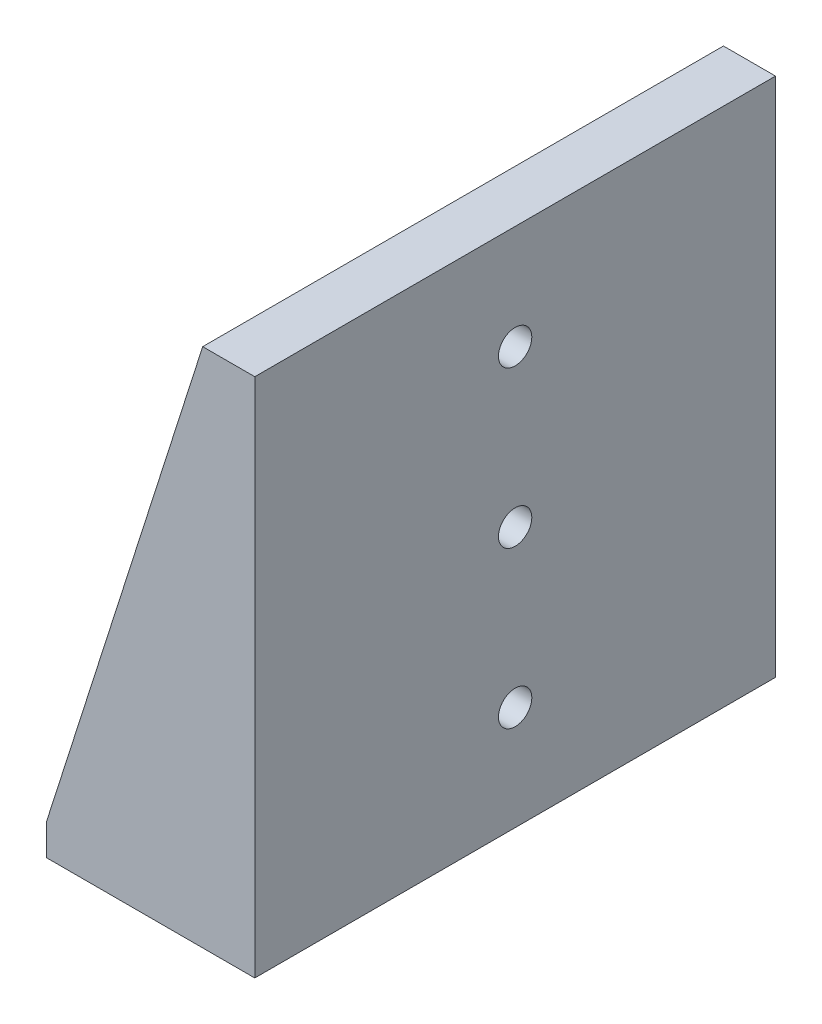
SolidWorks part; units mm, degrees
ref_plane "Front Plane" through (0, 0, 0) normal (0, 0, 1) x (1, 0, 0)
ref_plane "Top Plane" through (0, 0, 0) normal (0, 1, 0) x (1, 0, 0)
ref_plane "Right Plane" through (0, 0, 0) normal (1, 0, 0) x (0, 0, -1)
sketch "Sketch1" plane through (0, 0, 0) normal (0, 0, 1) x (1, 0, 0)
  line L0 (-10, 0) -> (10, 0)
  line L1 (-10, 0) -> (-10, 3)
  line L2 (-10, 3) -> (5, 50)
  line L3 (-10, 3) -> (23.3287, 3) construction
  line L4 (5, 50) -> (10, 50)
  line L5 (10, 0) -> (10, 50)
  point P4 (0, 0)
  dimension "D1" = 20
  dimension "D2" = 3
  dimension "D3" = 50
  dimension "D4" = 5
extrude "Boss-Extrude1" add sketch "Sketch1" along normal blind 50
sketch "Sketch3" plane through (-9.9445, 3.1738, 0) normal (-0.9527, 0.304, 0) x (0, 0, 1)
  line L0 (2.5, 49.1532) -> (2.5, -0.1824)
  line L1 (2.5, -0.1824) -> (47.5, -0.1824)
  line L2 (47.5, -0.1824) -> (47.5, 49.1532)
  line L3 (0, 49.1532) -> (0, -0.1824) construction
  line L4 (50, -0.1824) -> (0, -0.1824) construction
  line L5 (2.5, 49.1532) -> (47.5, 49.1532)
  line L6 (50, 49.1532) -> (0, 49.1532) construction
  line L7 (50, 49.1532) -> (50, -0.1824) construction
  dimension "D1" = 2.5
  dimension "D2" = 2.5
ref_plane "Plane1" through (-10, 0, 0) normal (-1, 0, 0) x (0, 0, 1)
sketch "Sketch4" plane through (-10, 0, 0) normal (-1, 0, 0) x (0, 0, 1)
  line L4 (2.5, 50) -> (2.5, 2.9986)
  line L5 (47.5, 2.9986) -> (47.5, 50)
  line L6 (2.5, 2.9986) -> (47.5, 2.9986)
  line L7 (2.5, 50) -> (47.5, 50)
  line L10 (50, 50) -> (0, 50) construction
  line L11 (50, 0) -> (0, 0) construction
  dimension "D1" = 2.5
  dimension "D2" = 2.5
  dimension "D3" = 2.9986
extrude "Cut-Extrude2" cut sketch "Sketch4" against normal up to vertex (15 mm away) up to point (5, 50, 2.5)
sketch "Sketch6" plane through (10, 0, 0) normal (1, 0, 0) x (0, 0, -1)
  line L0 (0, 10) -> (-50, 10) construction
  line L3 (0, 0) -> (0, 50) construction
  line L6 (-50, 0) -> (-50, 50) construction
  line L7 (0, 25) -> (-50, 25) construction
  line L8 (0, 40) -> (-50, 40) construction
  circle A0 centre (-25, 25) radius 1.6
  circle A1 centre (-25, 10) radius 1.6
  circle A2 centre (-25, 40) radius 1.6
  dimension "D1" = 3.2
  dimension "D4" = 3.2
  dimension "D5" = 3.2
  dimension "D2" = 15
  dimension "D3" = 15
extrude "Cut-Extrude4" cut sketch "Sketch6" against normal up to surface (5 mm away) up to face at (5, 26.4993, 25)
sketch "Sketch7" plane through (0, 2.9986, 0) normal (0, 1, 0) x (1, 0, 0)
  line L0 (-10, -25) -> (8, -25) construction
  line L3 (-7, -25) -> (3, -25) construction
  line L4 (-7, -24) -> (3, -24)
  line L5 (-7, -26) -> (3, -26)
  line L7 (-10, 0) -> (10, 0) construction
  arc A0 (-7, -24) -> (-7, -26) centre (-7, -25) ccw
  arc A1 (3, -26) -> (3, -24) centre (3, -25) ccw
  point P8 (-2, -25)
  dimension "D1" = 1
  dimension "D3" = 5
  dimension "D2" = 3
  dimension "D4" = 25
  dimension "D5" = 18
extrude "Cut-Extrude5" cut sketch "Sketch7" against normal up to surface (2.9986 mm away) up to face at (0, 0, 25)
fillet "Fillet1" radius 1 3 edges at (5, 2.9986, 25) (-2.5, 2.9986, 47.5) (-2.5, 2.9986, 2.5)
